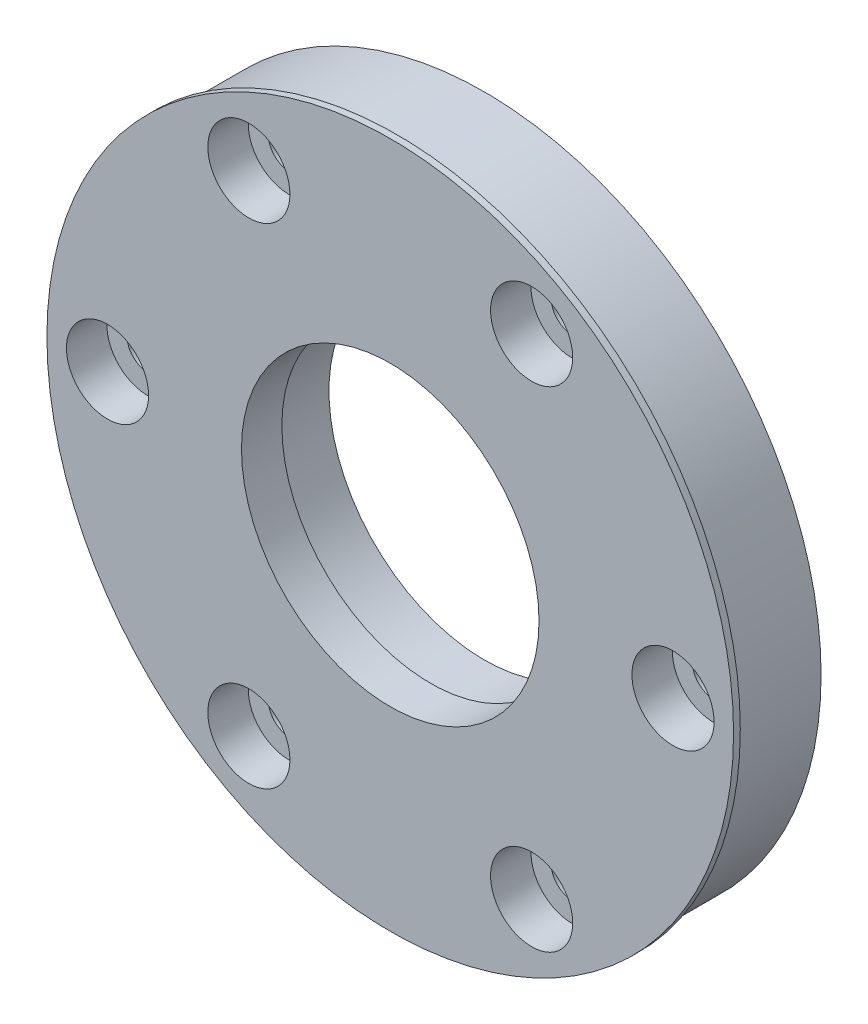
SolidWorks part; units mm, degrees
material "ABS"
ref_plane "Front Plane" through (0, 0, 0) normal (0, 0, 1) x (1, 0, 0)
ref_plane "Top Plane" through (0, 0, 0) normal (0, 1, 0) x (1, 0, 0)
ref_plane "Right Plane" through (0, 0, 0) normal (1, 0, 0) x (0, 0, -1)
sketch "Output Master Sketch" plane through (0, 0, 0) normal (0, 0, 1) x (1, 0, 0)
  circle A0 centre (0, 0) radius 21 construction
  circle A1 centre (21, 0) radius 3.05 construction
  circle A2 centre (10.5, -18.1865) radius 3.05 construction
  circle A3 centre (-10.5, -18.1865) radius 3.05 construction
  circle A4 centre (-21, 0) radius 3.05 construction
  circle A5 centre (-10.5, 18.1865) radius 3.05 construction
  circle A6 centre (10.5, 18.1865) radius 3.05 construction
  circle A7 centre (0, 0) radius 25
  point P17 (0, 0)
sketch "Sketch2" plane through (0, 0, 0) normal (0, 0, 1) x (1, 0, 0)
  circle A0 centre (0, 0) radius 25
  circle A1 centre (0, 0) radius 25 construction
  point P3 (0, 0)
extrude "Boss-Extrude1" add sketch "Sketch2" along normal blind 7
sketch "Sketch3" plane through (0, 0, 7) normal (0, 0, 1) x (1, 0, 0)
  circle A0 centre (-21, 0) radius 3.05
  circle A1 centre (-21, 0) radius 3.05 construction
  circle A2 centre (-10.5, 18.1865) radius 3.05
  circle A3 centre (10.5, 18.1865) radius 3.05
  circle A4 centre (21, 0) radius 3.05
  circle A5 centre (10.5, -18.1865) radius 3.05
  circle A6 centre (-10.5, -18.1865) radius 3.05
  point P5 (0, 0)
  point P18 (0, 0)
  dimension "D1" = 6.1
  dimension "D2" = 6
extrude "Dowel Pin Cutout" cut sketch "Sketch3" against normal blind 3
sketch "Sketch4" plane through (0, 0, 7) normal (0, 0, 1) x (1, 0, 0)
  circle A0 centre (0, 0) radius 25
  circle A1 centre (0, 0) radius 25.5
  circle A3 centre (0, 0) radius 25 construction
  dimension "D1" = 0.5
extrude "Main Housing Bearing Retainer" add sketch "Sketch4" against normal blind 0.5
sketch "Sketch5" plane through (0, 0, 0) normal (0, 0, -1) x (-1, 0, 0)
  circle A0 centre (-21, 0) radius 1.55
  circle A1 centre (-10.5, 18.1865) radius 1.55
  circle A2 centre (10.5, 18.1865) radius 1.55
  circle A3 centre (21, 0) radius 1.55
  circle A4 centre (10.5, -18.1865) radius 1.55
  circle A5 centre (-10.5, -18.1865) radius 1.55
  point P4 (20.4272, -1.3363)
  point P5 (0.3443, 0)
  point P15 (0, 0)
  point P16 (0, 0)
  dimension "D1" = 3.1
  dimension "D2" = 6
extrude "M3 Thru" cut sketch "Sketch5" against normal through all
sketch "Sketch6" plane through (0, 0, 0) normal (0, 0, -1) x (-1, 0, 0)
  circle A0 centre (-21, 0) radius 3
  circle A1 centre (-10.5, 18.1865) radius 3
  circle A2 centre (10.5, 18.1865) radius 3
  circle A3 centre (21, 0) radius 3
  circle A4 centre (10.5, -18.1865) radius 3
  circle A5 centre (-10.5, -18.1865) radius 3
  point P3 (0, 0)
  point P15 (0, 0)
  dimension "D1" = 6
  dimension "D2" = 6
extrude "M3 Button Head Cutout" cut sketch "Sketch6" against normal blind 1.7
sketch "Sketch8" plane through (0, 0, 7) normal (0, 0, 1) x (1, 0, 0)
  circle A0 centre (0, 0) radius 11.55
  dimension "D1" = 23.1
extrude "Input Shaft Bearing Cutout" cut sketch "Sketch8" against normal through all
sketch "Sketch9" plane through (0, 0, 0) normal (0, 0, -1) x (-1, 0, 0)
  circle A0 centre (0, 0) radius 11.55
  circle A1 centre (0, 0) radius 11.05
  circle A2 centre (0, 0) radius 11.55 construction
  dimension "D1" = 0.5
extrude "Input Shaft Bearing Retainer" add sketch "Sketch9" along normal blind 3 from surface starting at face at (11.55, 0, 7)
